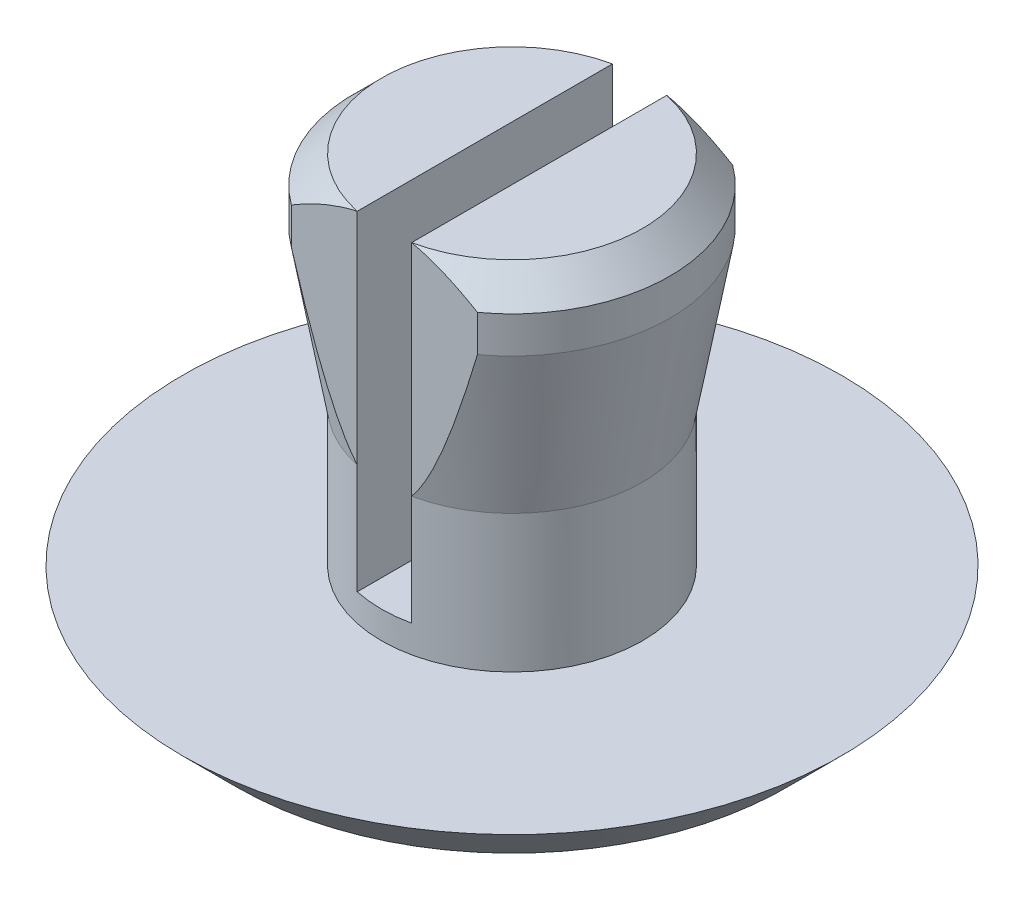
SolidWorks part; units mm, degrees
ref_plane "Front Plane" through (0, 0, 0) normal (0, 0, 1) x (1, 0, 0)
ref_plane "Top Plane" through (0, 0, 0) normal (0, 1, 0) x (1, 0, 0)
ref_plane "Right Plane" through (0, 0, 0) normal (1, 0, 0) x (0, 0, -1)
sketch "Sketch1" plane through (0, 0, 0) normal (0, 1, 0) x (1, 0, 0)
  circle A0 centre (0, 0) radius 4.75
extrude "Boss-Extrude1" add sketch "Sketch1" along normal blind 13
sketch "Sketch2" plane through (0, 0, 0) normal (0, -1, 0) x (1, 0, 0)
  circle A0 centre (0, 0) radius 12
extrude "Boss-Extrude2" add sketch "Sketch2" along normal blind 2
chamfer "Chamfer1" distance 2 angle 45 1 edges at (0, -2, -12)
sketch "Sketch4" plane through (0, 13, 0) normal (0, 1, 0) x (1, 0, 0)
  line L2 (-0.9896, -4.6458) -> (-0.9896, 4.6458)
  line L4 (0.9896, -4.6458) -> (0.9896, 4.6458)
  line L5 (-1, -7.5) -> (1, 7.5) construction
  line L6 (-1, 7.5) -> (1, -7.5) construction
  circle A0 centre (0, 0) radius 4.75 construction
  arc A1 (-0.9896, -4.6458) -> (0.9896, -4.6458) centre (0, 0) ccw
  arc A2 (0.9896, 4.6458) -> (-0.9896, 4.6458) centre (0, 0) ccw
  dimension "D1" = 15
  dimension "D2" = 2
extrude "Cut-Extrude1" cut sketch "Sketch4" against normal blind 12
sketch "Sketch5" plane through (0, 13, 0) normal (0, 1, 0) x (1, 0, 0)
  line L2 (1.1979, -4.6458) -> (3.3881, -4.6458)
  line L3 (-1.1979, -4.6458) -> (-3.3881, -4.6458)
  line L5 (1.1979, 4.6458) -> (3.3881, 4.6458)
  line L6 (-1.1979, 4.6458) -> (-3.3881, 4.6458)
  line L7 (0.9896, -4.6458) -> (0.9896, 4.6458) construction
  line L8 (-0.9896, 4.6458) -> (-0.9896, -4.6458) construction
  line L9 (0.9896, -4.6458) -> (0.9896, 4.6458)
  line L10 (-0.9896, 4.6458) -> (-0.9896, -4.6458)
  line L11 (1.1979, -4.6458) -> (0.9896, -4.6458)
  line L12 (-1.1979, -4.6458) -> (-0.9896, -4.6458)
  line L13 (-1.1979, 4.6458) -> (-0.9896, 4.6458)
  line L14 (1.1979, 4.6458) -> (0.9896, 4.6458)
  arc A5 (-1.1979, 5.6238) -> (-1.1979, -5.6238) centre (0, 0) ccw
  arc A6 (-3.3881, 4.6458) -> (-3.3881, -4.6458) centre (0, 0) ccw
  arc A8 (1.1979, -5.6238) -> (1.1979, 5.6238) centre (0, 0) ccw
  arc A9 (3.3881, -4.6458) -> (3.3881, 4.6458) centre (0, 0) ccw
  dimension "D1" = 1
  dimension "D2" = 1
extrude "Boss-Extrude3" add sketch "Sketch5" against normal blind 2
chamfer "Chamfer3" distance 6 angle 10 2 edges at (4.75, 11, 0) (-4.75, 11, 0) first distance on face at (0, 0, 4.75)
chamfer "Chamfer4" distance 1 angle 45 2 edges at (5.75, 13, 0) (-5.75, 13, 0)
